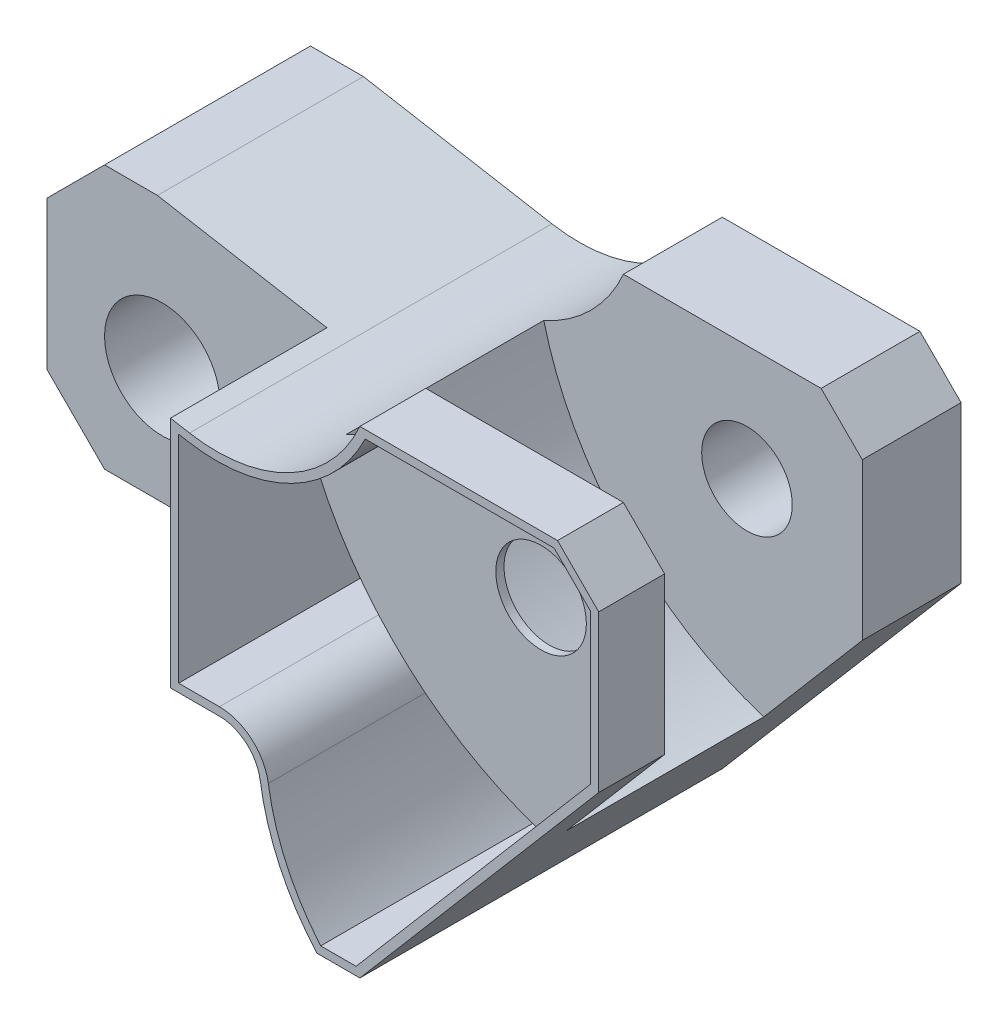
SolidWorks part; units mm, degrees
material "AISI 1020"
ref_plane "Front Plane" through (0, 0, 0) normal (0, 0, 1) x (1, 0, 0)
ref_plane "Top Plane" through (0, 0, 0) normal (0, 1, 0) x (1, 0, 0)
ref_plane "Right Plane" through (0, 0, 0) normal (1, 0, 0) x (0, 0, -1)
sketch "Sketch1" plane through (0, 0, 0) normal (0, 0, 1) x (1, 0, 0)
  line L0 (0, 0) -> (-7, 7)
  line L1 (-7, 7) -> (-7, 25)
  line L2 (-7, 25) -> (0, 32)
  line L3 (0, 32) -> (6.4231, 32)
  line L4 (50, 39) -> (74, 39)
  line L5 (74, 39) -> (79, 34)
  line L6 (79, 34) -> (79, 15)
  line L7 (79, 15) -> (50, -19)
  line L8 (50, -19) -> (44.7881, -19)
  line L10 (32.9488, 0) -> (0, 0)
  line L11 (-7, 14) -> (7, 14) construction
  line L12 (66.2059, -19) -> (66.2059, 0) construction
  line L13 (6.4231, 32) -> (16.9623, 32) construction
  line L14 (6.4231, 32) -> (29.3194, 27.9628)
  circle A0 centre (7, 14) radius 7
  arc A1 (37.8933, -4.2566) -> (32.9488, 0) centre (32.9488, -5) ccw
  arc A2 (44.7881, -19) -> (37.8933, -4.2566) centre (66.2059, 0) cw
  arc A3 (50, 39) -> (29.3194, 27.9628) centre (32.6187, 46.6741) cw
  point P26 (66.2059, 0)
  dimension "D5" = 45
  dimension "D17" = 5
  dimension "D20" = 10
  dimension "D21" = 19
  dimension "D1" = 7
  dimension "D2" = 32
  dimension "D3" = 14
  dimension "D4" = 14
  dimension "D6" = 19
  dimension "D7" = 14
  dimension "D8" = 7
  dimension "D9" = 45
  dimension "D10" = 14
  dimension "D11" = 29
  dimension "D12" = 45
  dimension "D13" = 5
  dimension "D14" = 24
  dimension "D15" = 86
  dimension "D16" = 58
  dimension "D18" = 19
  dimension "D19" = 29
extrude "Boss-Extrude1" add sketch "Sketch1" along normal blind 44
sketch "Sketch2" plane through (0, 0, 0) normal (0, 0, 1) x (1, 0, 0)
  line L0 (79, 39) -> (79, -0.8655) construction
  line L1 (50, -19) -> (79, 15) construction
  arc A0 (79, -0.8655) -> (37.6914, 28.3638) centre (79, 42.939) cw
  arc A1 (29.3194, 27.9628) -> (50, 39) centre (32.6187, 46.6741) ccw construction
  arc A2 (66.2059, 0) -> (36.7484, 28.0311) centre (79, 42.939) cw
ref_plane "Plane6" through (79, 0, 0) normal (1, 0, 0) x (0, 0, -1)
sketch "Sketch70" plane through (79, 0, 0) normal (1, 0, 0) x (0, 0, -1)
  line L0 (-44, 39) -> (0, 39) construction
  line L1 (-36, 39) -> (-12, 39)
  line L2 (-36, 39) -> (-36, -0.8655)
  line L3 (-36, -0.8655) -> (-12, -0.8655)
  line L4 (-12, 39) -> (-12, -0.8655)
  line L5 (-36, 39) -> (-12, -0.8655) construction
  line L6 (-36, -0.8655) -> (-12, 39) construction
  line L7 (-44, 15) -> (-44, 34) construction
  line L8 (0, 7) -> (0, 25) construction
  point P4 (-24, 19.0672)
  dimension "D1" = 12
  dimension "D2" = 24
revolve "Cut-Revolve3" cut sketch "Sketch70" angle 360 about L1
ref_plane "Plane8" through (0, 39, 0) normal (0, 1, 0) x (1, 0, 0)
sketch "Sketch71" plane through (0, 39, 0) normal (0, 1, 0) x (1, 0, 0)
  line L0 (-7, -44) -> (-7, 0) construction
  line L1 (-7, -25) -> (27, -25)
  line L2 (-7, -25) -> (-7, -44)
  line L3 (-7, -44) -> (27, -44)
  line L4 (27, -25) -> (27, -44)
  line L5 (-7, -25) -> (27, -44) construction
  line L6 (-7, -44) -> (27, -25) construction
  line L7 (29.3194, -44) -> (6.4231, -44) construction
  point P4 (10, -34.5)
  dimension "D1" = 19
  dimension "D2" = 34
extrude "Cut-Extrude1" cut sketch "Sketch71" against normal blind 43
sketch "Sketch73" plane through (0, 0, 0) normal (0, 0, 1) x (1, 0, 0)
  line L0 (50, 39) -> (74, 39) construction
  line L1 (79, 34) -> (79, 15) construction
  circle A0 centre (65, 25) radius 5.5
  point P0 (65, 25)
  dimension "D1" = 14
  dimension "D2" = 14
extrude "Cut-Extrude3" cut sketch "Sketch73" along normal through all contours A0
sketch "Sketch78" plane through (0, 0, 44) normal (0, 0, 1) x (1, 0, 0)
  line L16 (29.1458, 26.978) -> (28, 27.18)
  line L17 (28, 27.18) -> (28, 1)
  line L18 (28, 1) -> (32.9488, 1)
  line L19 (45.2426, -18) -> (49.5386, -18)
  line L20 (49.5386, -18) -> (78, 15.3685)
  line L21 (78, 15.3685) -> (78, 33.5858)
  line L22 (78, 33.5858) -> (73.5858, 38)
  line L23 (73.5858, 38) -> (50.6398, 38)
  line L24 (29.1458, 26.978) -> (28, 27.18)
  line L25 (28, 27.18) -> (28, 1)
  line L26 (28, 1) -> (32.9488, 1)
  line L27 (45.2426, -18) -> (49.5386, -18)
  line L28 (49.5386, -18) -> (78, 15.3685)
  line L29 (78, 15.3685) -> (78, 33.5858)
  line L30 (78, 33.5858) -> (73.5858, 38)
  line L31 (73.5858, 38) -> (50.6398, 38)
  arc A3 (36.9441, 27.1474) -> (66.2059, 0) centre (78.8576, 42.9811) ccw
  arc A6 (38.8822, -4.108) -> (32.9488, 1) centre (32.9488, -5) ccw
  arc A7 (38.8822, -4.108) -> (45.2426, -18) centre (66.2059, 0) ccw
  arc A8 (29.1458, 26.978) -> (50.6398, 38) centre (32.6187, 46.6741) ccw
  arc A9 (38.8822, -4.108) -> (32.9488, 1) centre (32.9488, -5) ccw
  arc A10 (38.8822, -4.108) -> (45.2426, -18) centre (66.2059, 0) ccw
  arc A11 (29.1458, 26.978) -> (50.6398, 38) centre (32.6187, 46.6741) ccw
  point P2 (18.1779, 29.2318)
  point P3 (0, 0)
  point P4 (0, 0)
  point P5 (0, 0)
  point P6 (0, 0)
  point P7 (0, 0)
  circle M12 centre (65, 25) radius 5.5
  dimension "D1" = 1
extrude "Cut-Extrude4" cut sketch "Sketch78" against normal blind 32 contours A11 L24 L25 L26 A9 A10 L27 L28 A3 region at (42.9954, 3.9566, 44)
extrude "Cut-Extrude5" cut sketch "Sketch78<14>" against normal blind 7 contours A11 A3 L28 L29 L30 L31 M12 region at (59.8502, 21.3299, 44)
sketch "Sketch78<14>" plane through (0, 0, 44) normal (0, 0, 1) x (1, 0, 0) same geometry as "Sketch78"
